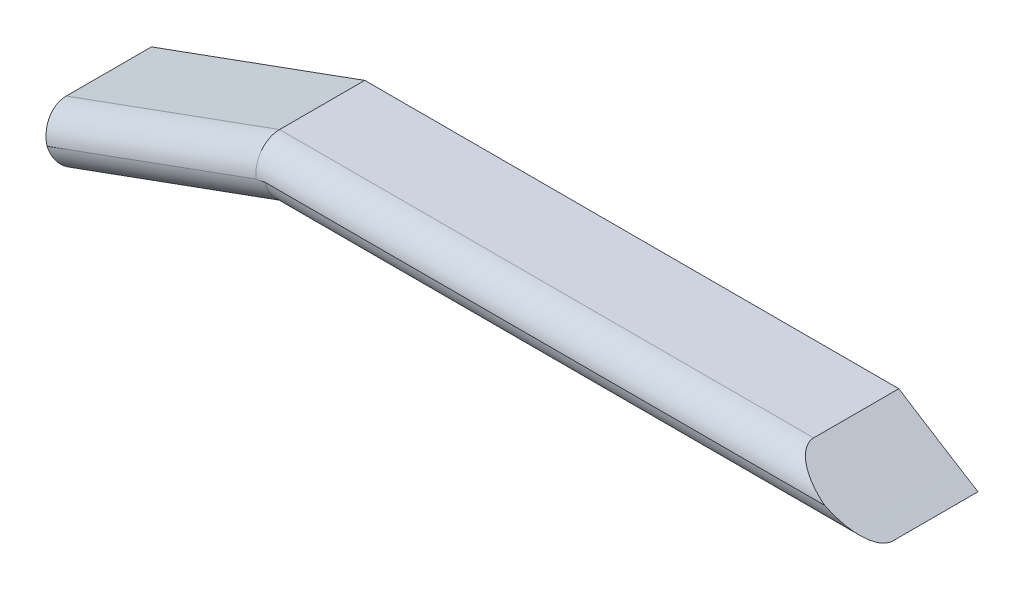
SolidWorks part; units mm, degrees
other "标注1"
sketch "草图3" plane through (-22.25, 4, -10) normal (-0.231, 0.6469, -0.7268) x (-0.9696, -0.2151, 0.1167)
other "标注2"
sketch "草图4" plane through (22.25, 8, -30) normal (0.0083, 0.0567, -0.9984) x (-0.9991, 0.0415, -0.0059)
ref_plane "前视基准面" through (0, 0, 0) normal (0, 0, 1) x (1, 0, 0)
ref_plane "上视基准面" through (0, 0, 0) normal (0, 1, 0) x (1, 0, 0)
ref_plane "右视基准面" through (0, 0, 0) normal (1, 0, 0) x (0, 0, -1)
other "Configuration Table"
sketch "草图1" plane through (0, 0, 0) normal (0, 1, 0) x (1, 0, 0)
  line L36 (0, -4) -> (20, -4)
  line L37 (0, -4) -> (0, 0)
  line L38 (0, 0) -> (20, 0)
  line L39 (20, -4) -> (20, 0)
  dimension "D1" = 4
  dimension "D2" = 20
extrude "凸台-拉伸1" add sketch "草图1" along normal blind 1.75
sketch "草图6" plane through (0, 0, 4) normal (0, 0, 1) x (1, 0, 0)
  line L0 (0, 1.75) -> (20, 1.75) construction
  line L1 (20, 1.75) -> (20, 0) construction
  line L2 (20, 0) -> (22.7902, 0)
  line L3 (0, 0) -> (20, 0) construction
  line L4 (20, 1.75) -> (20, 0)
  arc A0 (20, 1.75) -> (22.7902, 0) centre (135.3627, 182.5861) ccw
  dimension "D1" = 214.5
  dimension "D2" = 2.7902
extrude "凸台-拉伸2" add sketch "草图6" against normal up to surface (4 mm away) up to face at (10, 0.875, 0)
sketch "草图7" plane through (0, 0, 0) normal (0, 0, -1) x (-1, 0, 0)
  line L0 (5.6994, -2.7362) -> (-1.8181, 0)
  line L1 (-22.7902, 0) -> (0, 0) construction
  line L2 (0, 1.75) -> (0, 0) construction
  line L6 (-1.8181, 0) -> (-1.1812, 1.75)
  line L7 (-20, 1.75) -> (0, 1.75) construction
  line L8 (-1.1812, 1.75) -> (6.3363, -0.9862)
  line L9 (6.3363, -0.9862) -> (5.6994, -2.7362)
  point P2 (0, 0)
  dimension "D1" = 20
  dimension "D2" = 1.8181
  dimension "D3" = 8
extrude "凸台-拉伸3" add sketch "草图7" against normal up to surface (4 mm away) up to face at (10.6967, 0.8737, 4)
sketch "草图8" plane through (0, 0, 4) normal (0, 0, 1) x (1, 0, 0)
  line L0 (0, 1.3201) -> (-6.3363, -0.9862) construction
  line L2 (0, 1.75) -> (20, 1.75) construction
  line L3 (1.1812, 1.75) -> (-6.3363, -0.9862)
  line L4 (-6.3363, -0.9862) -> (0, 1.75)
  line L5 (0, 1.75) -> (1.1812, 1.75)
  point P0 (0.716, 1.75)
extrude "切除-拉伸1" cut sketch "草图8" against normal through all
fillet "圆角4" radius 1 4 edges at (-1.9406, -1.3681, 4) (12.3042, 0, 4) (-2.5776, 0.3819, 4) (10.5906, 1.75, 4)
